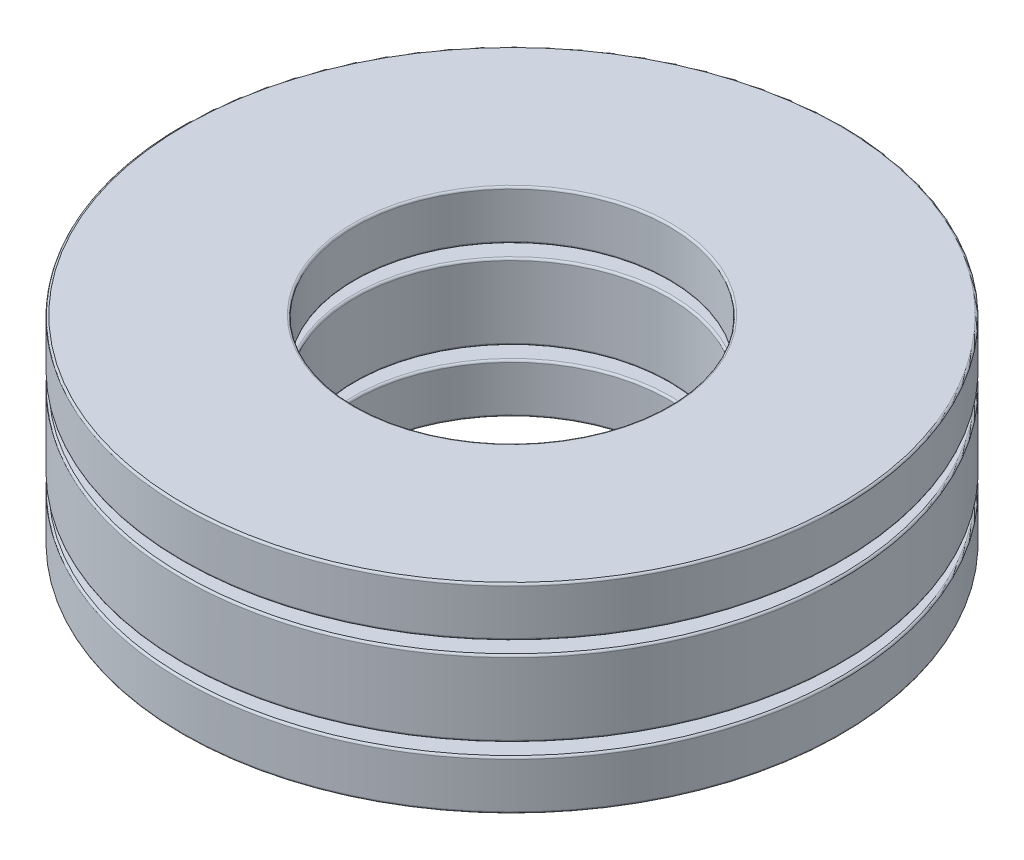
SolidWorks part; units mm, degrees
ref_plane "Front Plane" through (0, 0, 0) normal (0, 0, 1) x (1, 0, 0)
ref_plane "Top Plane" through (0, 0, 0) normal (0, 1, 0) x (1, 0, 0)
ref_plane "Right Plane" through (0, 0, 0) normal (1, 0, 0) x (0, 0, -1)
sketch "Sketch1" plane through (0, 0, 0) normal (0, 1, 0) x (1, 0, 0)
  circle A0 centre (0, 0) radius 10.5 construction
  circle A1 centre (0, 0) radius 5 construction
  circle A2 centre (0, 0) radius 7.55 construction
  dimension "B | OD" = 21
  dimension "A | ID" = 10
  dimension "C | Ball Circle" = 15.1
sketch "Sketch2" plane through (0, 0, 0) normal (0, 0, -1) x (-1, 0, 0)
  line L0 (-10.5, 3.175) -> (-10.5, 1.605) construction
  line L1 (-10.5, 0) -> (0, 0) construction
  line L3 (0, 3.175) -> (0, -3.175) construction
  line L4 (-10.5, 1.605) -> (-10.5, -1.605) construction
  line L6 (-10.5, -1.605) -> (-10.5, -3.175) construction
  point P11 (-10.5, 0)
  dimension "E | Thickness" = 6.35
  dimension "D | Washer Thickness" = 1.57
sketch "Sketch3" plane through (0, 0, 0) normal (0, 0, 1) x (1, 0, 0)
  line L2 (10.5, 1.2038) -> (5, 1.2038)
  line L4 (10.5, 1.2038) -> (10.5, -1.2037)
  line L7 (10.5, -1.2037) -> (5, -1.2037)
  line L8 (5, 1.2038) -> (5, -1.2037)
  line L11 (10.5, 1.605) -> (10.5, -1.605) construction
  point P8 (5, 0)
  dimension "D1" = 2.4075
revolve "Revolve1" add sketch "Sketch3" angle 360 about L3
sketch "Sketch4" plane through (0, 0, 0) normal (0, 0, 1) x (1, 0, 0)
  line L0 (7.55, 1.605) -> (7.55, -1.605)
  arc A0 (7.55, 1.605) -> (7.55, -1.605) centre (7.55, 0) ccw
revolve "Cut-Revolve1" cut sketch "Sketch4" angle 360 about L0
sketch "Sketch5" plane through (0, 0, 0) normal (0, 0, 1) x (1, 0, 0)
  line L0 (7.55, 1.605) -> (7.55, -1.605)
  arc A0 (7.55, 1.605) -> (7.55, -1.605) centre (7.55, 0) ccw
revolve "Revolve2" add sketch "Sketch5" angle 360 about L0
pattern_circular "CirPattern1" count 6 every 60 about axis through (0, 3.175, 0) along (0, -1, 0) of bodies 187
pattern_circular "CirPattern2" count 6 every 60 about axis through (0, 3.175, 0) along (0, -1, 0) of "Cut-Revolve1"
sketch "Sketch6" plane through (0, 0, 0) normal (0, 0, 1) x (1, 0, 0)
  line L2 (10.5, 3.175) -> (5, 3.175)
  line L3 (10.5, 3.175) -> (10.5, 1.605)
  line L4 (10.5, 1.605) -> (5, 1.605)
  line L5 (5, 3.175) -> (5, 1.605)
  line L6 (10.5, -1.605) -> (5, -1.605)
  line L7 (10.5, -1.605) -> (10.5, -3.175)
  line L8 (10.5, -3.175) -> (5, -3.175)
  line L13 (5, -1.605) -> (5, -3.175)
  point P11 (5, 0)
revolve "Revolve3" add sketch "Sketch6" angle 360 about L3
fillet "Fillet1" radius 0.0635 4 edges at (0, 1.605, 5) (0, 1.605, 10.5) (0, 3.175, 10.5) (0, 3.175, 5)
fillet "Fillet2" radius 0.0635 16 edges at (0, -1.2037, 5) (0, -1.2037, 10.5) (7.55, -1.2037, 1.0616) (2.8556, -1.2037, 7.0693) (-4.6944, -1.2037, 6.0077) (-7.55, -1.2037, -1.0616) (-2.8556, -1.2037, -7.0693) (4.6944, -1.2037, -6.0077) (0, 1.2038, 10.5) (0, 1.2038, 5) (7.55, 1.2038, -1.0616) (4.6944, 1.2038, 6.0077) (-2.8556, 1.2038, 7.0693) (-7.55, 1.2038, 1.0616) (-4.6944, 1.2038, -6.0077) (2.8556, 1.2038, -7.0693)
fillet "Fillet3" radius 0.0635 4 edges at (0, -1.605, 10.5) (0, -1.605, 5) (0, -3.175, 5) (0, -3.175, 10.5)
equation "\"Angle@CirPattern1\" = 360/\"Balls@CirPattern1\""
equation "\"D1@CirPattern2\" = \"Balls@CirPattern1\""
equation "\"D2@CirPattern2\" = \"Angle@CirPattern1\""
equation "\"D1@Sketch3\"=(\"E | Thickness@Sketch2\"-(2*\"D | Washer Thickness@Sketch2\"))*.75"
equation "\"D1@Fillet1\"=\"E | Thickness@Sketch2\" * .01"
equation "\"D1@Fillet2\"=\"D1@Fillet1\""
equation "\"D1@Fillet3\"=\"D1@Fillet1\""
